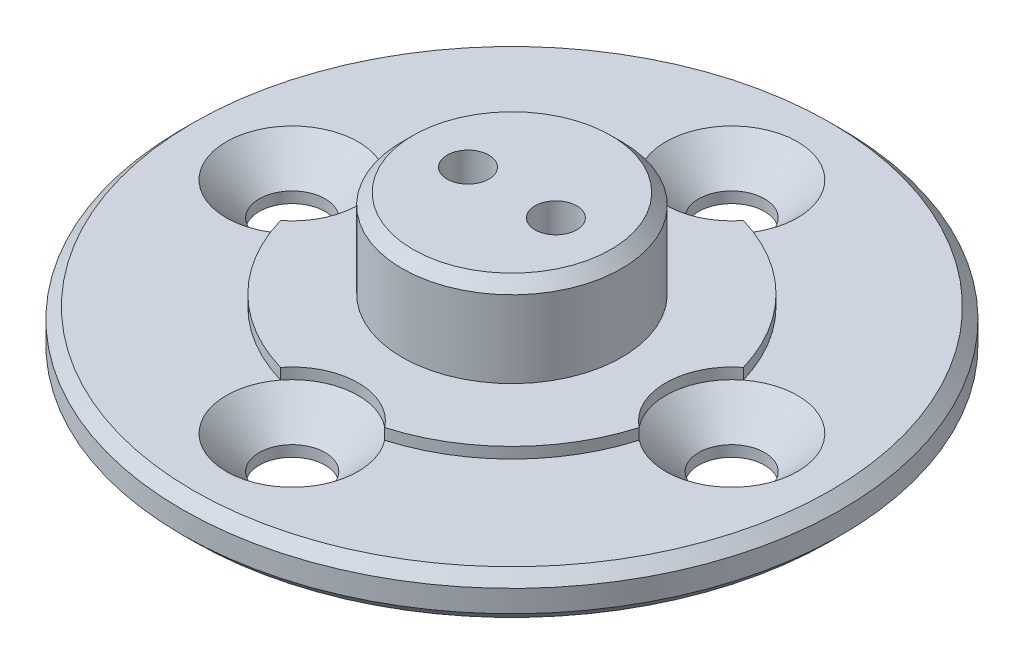
SolidWorks part; units mm, degrees
ref_plane "前视基准面" through (0, 0, 0) normal (0, 0, 1) x (1, 0, 0)
ref_plane "上视基准面" through (0, 0, 0) normal (0, 1, 0) x (1, 0, 0)
ref_plane "右视基准面" through (0, 0, 0) normal (1, 0, 0) x (0, 0, -1)
other "Configuration Table"
sketch "草图1" plane through (0, 0, 0) normal (0, 1, 0) x (1, 0, 0)
  line L0 (-21.98, 0) -> (22.6908, 0) construction
  line L1 (0, 22.7485) -> (0, -21.9381) construction
  circle A0 centre (0, 0) radius 15
  circle A1 centre (0, 10) radius 1.5
  circle A2 centre (10, 0) radius 1.5
  circle A3 centre (0, -10) radius 1.5
  circle A4 centre (-10, 0) radius 1.5
  point P15 (0, 0)
  dimension "D1" = 3
  dimension "D3" = 30
  dimension "D2" = 10
extrude "凸台-拉伸1" add sketch "草图1" along normal blind 2
sketch "草图2" plane through (0, 2, 0) normal (0, 1, 0) x (1, 0, 0)
  line L0 (0, 1.9211) -> (0, -1.7964) construction
  line L1 (-1.959, 0) -> (1.7076, 0) construction
  circle A1 centre (0, 0) radius 5
  circle A3 centre (2, 0) radius 0.95
  circle A4 centre (-2, 0) radius 0.95
  dimension "D1" = 10
  dimension "D2" = 1.9
  dimension "D3" = 4
extrude "凸台-拉伸2" add sketch "草图2" along normal blind 4.5
sketch "草图4" plane through (0, 2, 0) normal (0, 1, 0) x (1, 0, 0)
  arc A0 (-8.1625, -2.3714) -> (-2.3714, -8.1625) centre (0, 0) ccw
  arc A1 (-2.3714, 8.1625) -> (2.3714, 8.1625) centre (0, 10) ccw
  arc A2 (8.1625, 2.3714) -> (8.1625, -2.3714) centre (10, 0) ccw
  arc A3 (2.3714, -8.1625) -> (-2.3714, -8.1625) centre (0, -10) ccw
  arc A4 (-8.1625, -2.3714) -> (-8.1625, 2.3714) centre (-10, 0) ccw
  arc A5 (-2.3714, 8.1625) -> (-8.1625, 2.3714) centre (0, 0) ccw
  arc A6 (8.1625, 2.3714) -> (2.3714, 8.1625) centre (0, 0) ccw
  arc A7 (2.3714, -8.1625) -> (8.1625, -2.3714) centre (0, 0) ccw
  point P15 (0, 0)
  dimension "D1" = 17
  dimension "D2" = 6
  dimension "D3" = 4
extrude "凸台-拉伸3" add sketch "草图4" along normal blind 0.5
chamfer "倒角1" distance 0.5 angle 45 1 edges at (0, 6.5, 5)
chamfer "倒角2" distance 1.5 angle 45 4 edges at (10, 2, 1.5) (0, 2, 11.5) (-10, 2, 1.5) (0, 2, -8.5)
chamfer "倒角3" distance 0.5 angle 45 2 edges at (0, 0, 15) (0, 2, 15)
